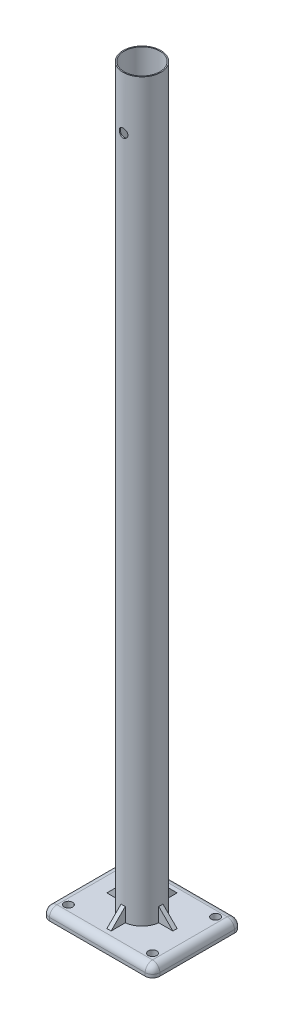
SolidWorks part; units mm, degrees
ref_plane "Front Plane" through (0, 0, 0) normal (0, 0, 1) x (1, 0, 0)
ref_plane "Top Plane" through (0, 0, 0) normal (0, 1, 0) x (1, 0, 0)
ref_plane "Right Plane" through (0, 0, 0) normal (1, 0, 0) x (0, 0, -1)
sketch "Sketch1" plane through (0, 0, 0) normal (0, 1, 0) x (1, 0, 0)
  line L1 (52.5, -42.5) -> (-52.5, -42.5)
  line L2 (52.5, -42.5) -> (52.5, 42.5)
  line L3 (52.5, 42.5) -> (-52.5, 42.5)
  line L4 (-52.5, -42.5) -> (-52.5, 42.5)
  line L5 (52.5, -42.5) -> (-52.5, 42.5) construction
  line L6 (52.5, 42.5) -> (-52.5, -42.5) construction
  line L7 (40, -30) -> (-40, -30) construction
  line L8 (40, -30) -> (40, 30) construction
  line L9 (40, 30) -> (-40, 30) construction
  line L10 (-40, -30) -> (-40, 30) construction
  line L11 (40, -30) -> (-40, 30) construction
  line L12 (40, 30) -> (-40, -30) construction
  circle A2 centre (-40, -30) radius 4
  circle A3 centre (40, 30) radius 4
  circle A4 centre (40, -30) radius 4
  circle A5 centre (-40, 30) radius 4
  point P0 (0, 0)
  point P6 (0, 0)
  dimension "D3" = 60
  dimension "D5" = 8
  dimension "D1" = 85
  dimension "D2" = 105
  dimension "D4" = 80
extrude "Boss-Extrude1" add sketch "Sketch1" along normal blind 10
sketch "Sketch16" plane through (0, 0, 0) normal (0, 0, 1) x (1, 0, 0)
  line L0 (36.0762, 10.055) -> (-3.0211, 63.3047)
fillet "Fillet1" radius 7 4 edges at (52.5, 10, 0) (-52.5, 10, 0) (52.5, 5, 42.5) (-52.5, 5, 42.5)
fillet "Fillet2" radius 7 8 edges at (50.4497, 7.9497, -42.5) (-50.4497, 7.9497, -42.5) (-50.4497, 7.9497, 40.4497) (50.4497, 7.9497, 40.4497) (0, 10, -42.5) (0, 10, 42.5) (52.5, 1.5, -42.5) (-52.5, 1.5, -42.5)
sketch "Sketch17" plane through (0, 10, 0) normal (0, 1, 0) x (1, 0, 0)
  circle A0 centre (0, 0) radius 18
  circle A1 centre (0, 0) radius 17
  point P4 (0, 0)
  point P5 (0, 0)
  dimension "D1" = 36
  dimension "D2" = 34
extrude "Boss-Extrude2" add sketch "Sketch17" along normal blind 700
sketch "Sketch18" plane through (0, 0, 0) normal (0, 0, 1) x (1, 0, 0)
  line L0 (-17.6279, 23.7966) -> (-31.418, 10.0065)
rib "Rib2" sketch "Sketch18" sketch "Sketch18" thickness 4 extrusion direction parallel to sketch draft on no parameters "D1"=4
pattern_circular "CirPattern1" count 4 over 360 about axis through (0, 710, 0) along (0, 1, 0) of "Rib2"
rib "Rib1" [suppressed] sketch "Sketch16" sketch "Sketch16" thickness 10 extrusion direction parallel to sketch draft on no parameters "D1"=10
ref_plane "Plane1" through (0, 0, 18) normal (0, 0, 1) x (1, 0, 0)
sketch "Sketch19" plane through (0, 0, 18) normal (0, 0, 1) x (1, 0, 0)
  line L0 (18, 710) -> (-18, 710) construction
  line L1 (18, 710) -> (-18, 710) construction
  line L2 (-18, 710) -> (-18, 23.4245) construction
  line L3 (-18, 710) -> (-18, 23.4245) construction
  line L4 (18, 23.4245) -> (18, 710) construction
  line L5 (18, 23.4245) -> (18, 710) construction
  line L6 (0, 720.8697) -> (0, 650.7017) construction
  circle A0 centre (0, 660) radius 4.1
  dimension "D1" = 8.2
  dimension "D2" = 50
extrude "Cut-Extrude1" cut sketch "Sketch19" against normal up to next
